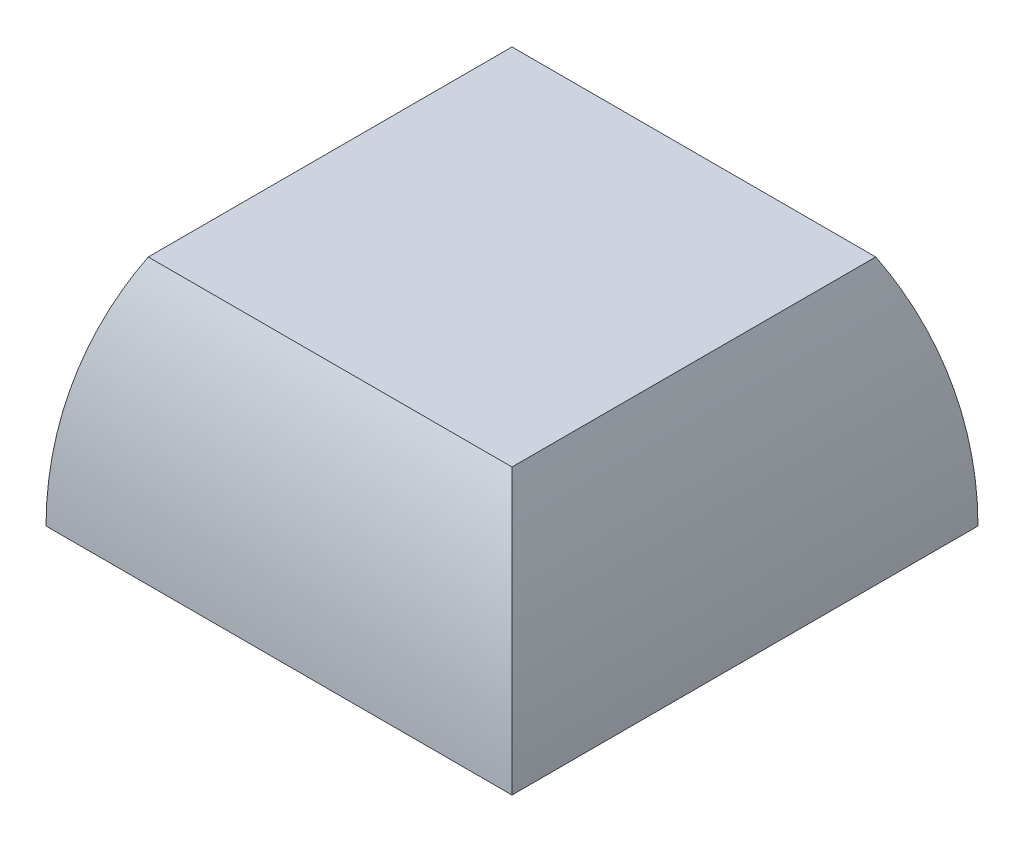
SolidWorks part; units mm, degrees
ref_plane "Front Plane" through (0, 0, 0) normal (0, 0, 1) x (1, 0, 0)
ref_plane "Top Plane" through (0, 0, 0) normal (0, 1, 0) x (1, 0, 0)
ref_plane "Right Plane" through (0, 0, 0) normal (1, 0, 0) x (0, 0, -1)
sketch "Sketch1" plane through (0, 0, 0) normal (0, 1, 0) x (1, 0, 0)
  line L0 (-6.5, 6.5) -> (6.5, 6.5)
  line L1 (-7.5, -7.5) -> (7.5, -7.5)
  line L2 (-7.5, -7.5) -> (-7.5, 7.5)
  line L3 (-7.5, 7.5) -> (7.5, 7.5)
  line L4 (7.5, -7.5) -> (7.5, 7.5)
  line L5 (-7.5, -7.5) -> (7.5, 7.5) construction
  line L6 (-7.5, 7.5) -> (7.5, -7.5) construction
  line L7 (6.5, -6.5) -> (6.5, 6.5)
  line L8 (-6.5, -6.5) -> (6.5, -6.5)
  line L9 (-6.5, -6.5) -> (-6.5, 6.5)
  circle A0 centre (0, 0) radius 2
  point P0 (0, 0)
  dimension "D3" = 4
  dimension "D1" = 15
  dimension "D2" = 1
extrude "Boss-Extrude1" add sketch "Sketch1" along normal blind 7.5 contours L1 L4 L3 L2 L8 L9 L0 L7 | L9 L8 L7 L0 A0 | A0 region at (0, 0, -6.3162) region at (-7.2879, 0, 0) region at (0, 0, 0)
sketch "Sketch2" plane through (0, 0, 0) normal (0, 0, 1) x (1, 0, 0)
  line L0 (7.5, 7.5) -> (7.5, 0) construction
  line L1 (-10, 0) -> (10, 0)
  line L2 (-10, 0) -> (-10, 12)
  line L3 (10, 0) -> (10, 12)
  line L4 (-10, 12) -> (10, 12)
  ellipse E0 centre (0, 0) end of major axis (0, 12) minor radius 7.5
  dimension "D1" = 12
  dimension "D2" = 20
extrude "Cut-Extrude1" cut sketch "Sketch2" against normal through all both and the other way through all contours E0 L4 L2 L1 | E0 L1 L3 L4 region at (-7.6043, 7.3001, 0) region at (7.6043, 7.3001, 0)
sketch "Sketch3" plane through (0, 0, 0) normal (1, 0, 0) x (0, 0, -1)
  line L0 (10, 0) -> (-10, 0)
  line L1 (10, 0) -> (10, 12)
  line L2 (-10, 0) -> (-10, 12)
  line L3 (10, 12) -> (-10, 12)
  ellipse E0 centre (0, 0) end of major axis (0, -12) minor radius 7.5
  dimension "D1" = 12
  dimension "D2" = 20
extrude "Cut-Extrude2" cut sketch "Sketch3" against normal through all both and the other way through all contours E0 L0 L1 L3 | E0 L3 L2 L0 region at (0, 7.3001, -7.6043) region at (0, 7.3001, 7.6043)
extrude "Cut-Extrude3" cut sketch "Sketch1<3>" along normal blind 5 contours L9 L8 L7 L0 A0 region at (0, 0, -6.3162)
sketch "Sketch1<3>" plane through (0, 0, 0) normal (0, 1, 0) x (1, 0, 0) same geometry as "Sketch1"
